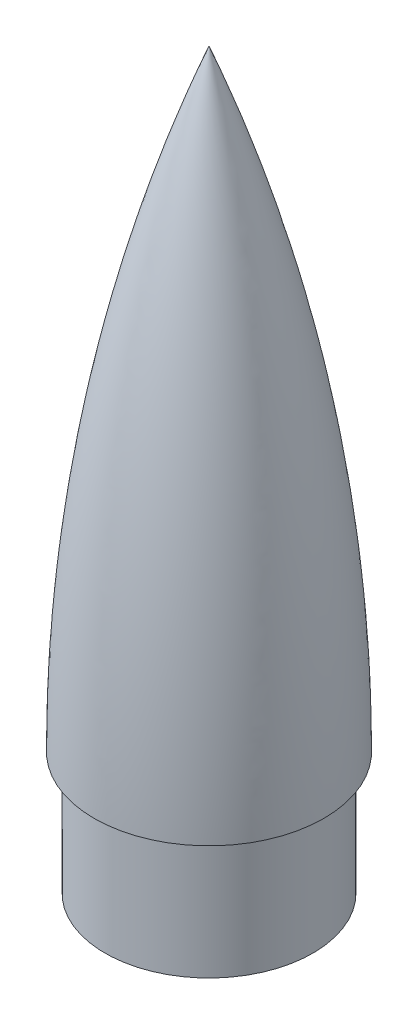
SolidWorks part; units mm, degrees
ref_plane "Front Plane" through (0, 0, 0) normal (0, 0, 1) x (1, 0, 0)
ref_plane "Top Plane" through (0, 0, 0) normal (0, 1, 0) x (1, 0, 0)
ref_plane "Right Plane" through (0, 0, 0) normal (1, 0, 0) x (0, 0, -1)
sketch "Sketch1" plane through (0, 0, 0) normal (0, 0, 1) x (1, 0, 0)
  line L0 (0, 0) -> (-28.2, 0) construction
  line L1 (0, 0) -> (0, 150) construction
  line L2 (0, 0) -> (209.8336, 0) construction
  line L3 (0, 150) -> (0, 135.6268)
  line L4 (-28.2, 0) -> (-23.2, 0)
  line L5 (-25.5, 0) -> (-25.5, -30)
  line L6 (-25.5, -30) -> (-23.9, -30)
  line L7 (-23.9, -30) -> (-21.4181, 38.0915)
  circle A0 centre (384.8362, 0) radius 413.0362
  circle A1 centre (384.8362, 0) radius 408.0362
  dimension "D1" = 28.2
  dimension "D2" = 150
  dimension "D4" = 1.6
  dimension "D5" = 25.5
  dimension "D6" = 30
  dimension "D7" = 87.913
  dimension "D3" = 5
revolve "Revolve1" add sketch "Sketch1" angle 360 about L1 region at (-17.1258, 72.2884, 0) region at (-24.4419, -14.0338, 0)
sketch "Sketch2" plane through (0, 0, 0) normal (1, 0, 0) x (0, 0, -1)
  line L0 (0, 50) -> (0, 0) construction
  circle A0 centre (0, 50) radius 5
  dimension "D1" = 10
  dimension "D2" = 50
extrude "Boss-Extrude1" add sketch "Sketch2" along normal up to body and the other way up to next
fillet "Fillet1" radius 3 2 edges at (-19.3292, 52.5563, 4.2971) (19.3672, 53.8038, 3.2451)
